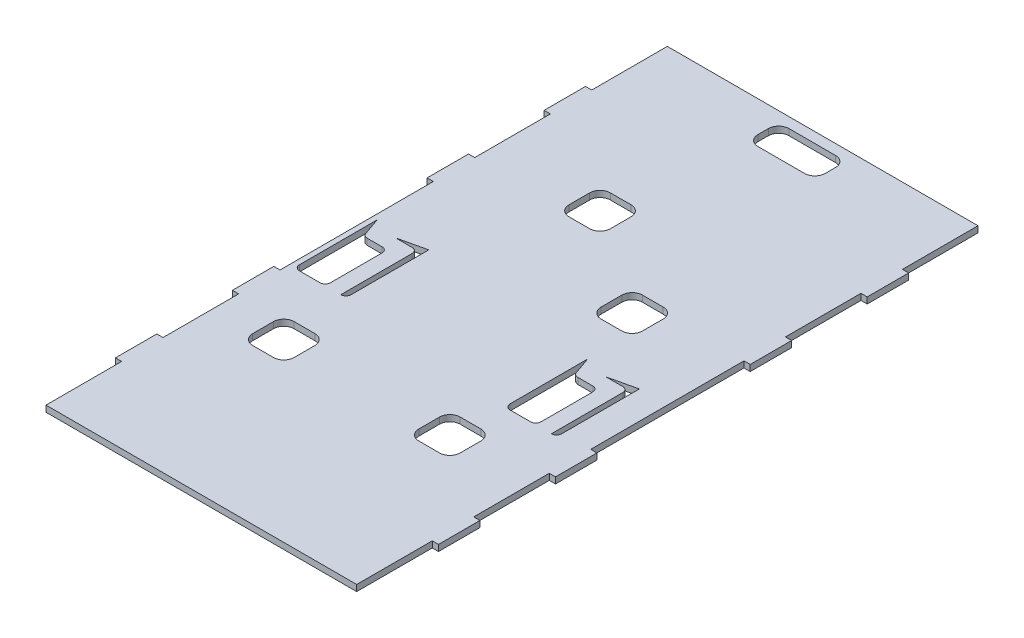
SolidWorks part; units mm, degrees
ref_plane "Front Plane" through (0, 0, 0) normal (0, 0, 1) x (1, 0, 0)
ref_plane "Top Plane" through (0, 0, 0) normal (0, 1, 0) x (1, 0, 0)
ref_plane "Right Plane" through (0, 0, 0) normal (1, 0, 0) x (0, 0, -1)
sketch "Sketch1" plane through (0, 0, 0) normal (0, 1, 0) x (1, 0, 0)
  line L0 (-157.4085, 145.5571) -> (-157.4085, 72.5571)
  line L1 (-157.4085, 258.5571) -> (142.5915, 258.5571)
  line L2 (-157.4085, 258.5571) -> (-157.4085, 185.5571)
  line L3 (-157.4085, -341.4429) -> (142.5915, -341.4429)
  line L4 (142.5915, 258.5571) -> (142.5915, 185.5571)
  line L9 (-157.4085, 185.5571) -> (-163.4085, 185.5571)
  line L11 (-157.4085, 145.5571) -> (-163.4085, 145.5571)
  line L12 (-163.4085, 185.5571) -> (-163.4085, 145.5571)
  line L13 (-157.4085, 72.5571) -> (-163.4085, 72.5571)
  line L15 (-157.4085, 32.5571) -> (-163.4085, 32.5571)
  line L16 (-163.4085, 72.5571) -> (-163.4085, 32.5571)
  line L17 (-157.4085, -115.4429) -> (-163.4085, -115.4429)
  line L19 (-157.4085, -155.4429) -> (-163.4085, -155.4429)
  line L20 (-163.4085, -115.4429) -> (-163.4085, -155.4429)
  line L21 (-157.4085, -228.4429) -> (-163.4085, -228.4429)
  line L23 (-157.4085, -268.4429) -> (-163.4085, -268.4429)
  line L24 (-163.4085, -228.4429) -> (-163.4085, -268.4429)
  line L25 (-157.4085, 32.5571) -> (-157.4085, -115.4429)
  line L26 (-157.4085, -155.4429) -> (-157.4085, -228.4429)
  line L27 (-157.4085, -268.4429) -> (-157.4085, -341.4429)
  line L28 (142.5915, 145.5571) -> (142.5915, 72.5571)
  line L29 (142.5915, 185.5571) -> (148.5915, 185.5571)
  line L31 (142.5915, 145.5571) -> (148.5915, 145.5571)
  line L32 (148.5915, 185.5571) -> (148.5915, 145.5571)
  line L33 (142.5915, 72.5571) -> (148.5915, 72.5571)
  line L35 (142.5915, 32.5571) -> (148.5915, 32.5571)
  line L36 (148.5915, 72.5571) -> (148.5915, 32.5571)
  line L37 (142.5915, -115.4429) -> (148.5915, -115.4429)
  line L39 (142.5915, -155.4429) -> (148.5915, -155.4429)
  line L40 (148.5915, -115.4429) -> (148.5915, -155.4429)
  line L41 (142.5915, -228.4429) -> (148.5915, -228.4429)
  line L43 (142.5915, -268.4429) -> (148.5915, -268.4429)
  line L44 (148.5915, -228.4429) -> (148.5915, -268.4429)
  line L45 (142.5915, 32.5571) -> (142.5915, -115.4429)
  line L46 (142.5915, -155.4429) -> (142.5915, -228.4429)
  line L47 (142.5915, -268.4429) -> (142.5915, -341.4429)
  dimension "D1" = 600
  dimension "D2" = 300
  dimension "D3" = 73
  dimension "D4" = 40
  dimension "D5" = 73
  dimension "D6" = 40
  dimension "D7" = 40
  dimension "D8" = 40
  dimension "D9" = 73
  dimension "D10" = 73
  dimension "D11" = 73
  dimension "D12" = 73
  dimension "D13" = 40
  dimension "D14" = 40
  dimension "D15" = 40
  dimension "D16" = 40
  dimension "D17" = 73
  dimension "D18" = 73
  dimension "D19" = 6
  dimension "D20" = 6
  dimension "D21" = 6
  dimension "D22" = 6
  dimension "D23" = 6
  dimension "D24" = 6
  dimension "D25" = 6
  dimension "D26" = 6
extrude "Boss-Extrude1" add sketch "Sketch1" along normal blind 6
sketch "Sketch2" plane through (0, 6, 0) normal (0, 1, 0) x (1, 0, 0)
  line L0 (-17.4085, -341.4429) -> (-17.4085, -191.4429) construction
  line L2 (-157.4085, -341.4429) -> (142.5915, -341.4429) construction
  line L4 (-17.4085, -191.4429) -> (-157.4085, -191.9429) construction
  line L5 (-157.4085, -155.4429) -> (-157.4085, -228.4429) construction
  line L7 (-17.4085, -191.4429) -> (152.9941, -191.4429) construction
  line L9 (-117.4085, -191.8) -> (-77.4085, -191.8)
  line L10 (-117.4085, -191.8) -> (-117.4085, -151.8)
  line L11 (-117.4085, -151.8) -> (-77.4085, -151.8)
  line L12 (-77.4085, -191.8) -> (-77.4085, -151.8)
  line L13 (42.5915, -191.4429) -> (82.5915, -191.4429)
  line L14 (42.5915, -191.4429) -> (42.5915, -151.4429)
  line L15 (42.5915, -151.4429) -> (82.5915, -151.4429)
  line L16 (82.5915, -191.4429) -> (82.5915, -151.4429)
  dimension "D1" = 140
  dimension "D2" = 150
  dimension "D3" = 40
  dimension "D4" = 40
  dimension "D5" = 40
  dimension "D6" = 40
  dimension "D7" = 120
  dimension "D8" = 60
extrude "Cut-Extrude1" cut sketch "Sketch2" against normal blind 10
fillet "Fillet1" radius 10 8 edges at (42.5915, 3, 191.4429) (42.5915, 3, 151.4429) (82.5915, 3, 151.4429) (82.5915, 3, 191.4429) (-77.4085, 3, 191.8) (-117.4085, 3, 191.8) (-77.4085, 3, 151.8) (-117.4085, 3, 151.8)
sketch "Sketch3" plane through (0, 6, 0) normal (0, 1, 0) x (1, 0, 0)
  line L4 (-102.4085, -26.8) -> (-102.4085, -106.8)
  line L5 (-152.4085, -106.8) -> (-122.4085, -106.8)
  line L7 (-122.4085, -106.8) -> (-122.4085, -46.8)
  line L8 (-122.4085, -46.8) -> (-145.4085, -46.8)
  line L9 (-145.4085, -46.8) -> (-152.4085, -26.8)
  line L10 (-102.4085, -106.8) -> (-107.4085, -106.8)
  line L12 (-107.4085, -32.8) -> (-128.4085, -32.8)
  line L13 (-128.4085, -32.8) -> (-102.4085, -26.8)
  line L15 (-152.4085, -26.8) -> (-152.4085, -106.8)
  line L16 (-157.4085, 32.5571) -> (-157.4085, -115.4429) construction
  line L17 (-107.4085, -32.8) -> (-107.4085, -106.8)
  line L18 (-87.4085, -151.8) -> (-107.4085, -151.8) construction
  dimension "D2" = 80
  dimension "D3" = 50
  dimension "D4" = 80
  dimension "D5" = 30
  dimension "D6" = 5
  dimension "D7" = 23
  dimension "D8" = 21
  dimension "D9" = 14
  dimension "D10" = 60
  dimension "D11" = 45
  dimension "D12" = 5
  dimension "D13" = 45
  dimension "D14" = 7.8102
sketch "Sketch4" plane through (0, 6, 0) normal (0, 1, 0) x (1, 0, 0)
  line L2 (65.5915, -41.4429) -> (65.5915, -121.4429)
  line L6 (72.5915, -61.4429) -> (95.5915, -61.4429)
  line L7 (65.5915, -41.4429) -> (72.5915, -61.4429)
  line L8 (95.5915, -61.4429) -> (95.5915, -121.4429)
  line L9 (65.5915, -121.4429) -> (95.5915, -121.4429)
  line L11 (115.5915, -41.4429) -> (89.5915, -47.4429)
  line L12 (89.5915, -47.4429) -> (110.5915, -47.4429)
  line L13 (110.5915, -47.4429) -> (110.5915, -121.4429)
  line L15 (110.5915, -121.4429) -> (115.5915, -121.4429)
  line L16 (115.5915, -41.4429) -> (115.5915, -121.4429)
  dimension "D1" = 80
  dimension "D2" = 50
  dimension "D3" = 14
  dimension "D4" = 60
  dimension "D5" = 50
  dimension "D6" = 30
  dimension "D8" = 23
  dimension "D9" = 21
  dimension "D10" = 5
extrude "Cut-Extrude4" cut sketch "Sketch3" against normal blind 16
fillet "Fillet2" radius 5 3 edges at (-107.4085, 3, 32.8) (-122.4085, 3, 46.8) (-145.4085, 3, 46.8)
fillet "Fillet3" radius 5 3 edges at (-102.4085, 3, 106.8) (-122.4085, 3, 106.8) (-152.4085, 3, 106.8)
extrude "Cut-Extrude5" cut sketch "Sketch4" against normal blind 16
fillet "Fillet4" radius 5 6 edges at (95.5915, 3, 61.4429) (115.5915, 3, 121.4429) (95.5915, 3, 121.4429) (65.5915, 3, 121.4429) (110.5915, 3, 47.4429) (72.5915, 3, 61.4429)
sketch "Sketch5" plane through (0, 6, 0) normal (0, 1, 0) x (1, 0, 0)
  line L0 (-52.4085, -341.4429) -> (-52.4085, 88.5571) construction
  line L1 (-157.4085, -341.4429) -> (142.5915, -341.4429) construction
  line L3 (48.5915, -341.4429) -> (48.5915, 18.5571) construction
  line L4 (48.5915, 18.5571) -> (142.5915, 18.5571) construction
  line L5 (142.5915, -115.4429) -> (142.5915, 32.5571) construction
  line L6 (-52.4085, 88.5571) -> (-157.4085, 88.5571) construction
  line L7 (-157.4085, 145.5571) -> (-157.4085, 72.5571) construction
  line L9 (-72.4085, 68.5571) -> (-32.4085, 68.5571)
  line L10 (-72.4085, 68.5571) -> (-72.4085, 108.5571)
  line L11 (-72.4085, 108.5571) -> (-32.4085, 108.5571)
  line L12 (-32.4085, 68.5571) -> (-32.4085, 108.5571)
  line L13 (-72.4085, 68.5571) -> (-32.4085, 108.5571) construction
  line L14 (-72.4085, 108.5571) -> (-32.4085, 68.5571) construction
  line L15 (68.5915, -1.4429) -> (28.5915, -1.4429)
  line L16 (68.5915, -1.4429) -> (68.5915, 38.5571)
  line L17 (68.5915, 38.5571) -> (28.5915, 38.5571)
  line L18 (28.5915, -1.4429) -> (28.5915, 38.5571)
  line L19 (68.5915, -1.4429) -> (28.5915, 38.5571) construction
  line L20 (68.5915, 38.5571) -> (28.5915, -1.4429) construction
  dimension "D1" = 430
  dimension "D2" = 105
  dimension "D3" = 94
  dimension "D4" = 360
  dimension "D5" = 40
  dimension "D6" = 40
  dimension "D7" = 40
  dimension "D8" = 40
extrude "Cut-Extrude6" cut sketch "Sketch5" against normal blind 16
fillet "Fillet5" radius 10 8 edges at (68.5915, 3, -38.5571) (68.5915, 3, 1.4429) (28.5915, 3, -38.5571) (28.5915, 3, 1.4429) (-72.4085, 3, -68.5571) (-32.4085, 3, -108.5571) (-32.4085, 3, -68.5571) (-72.4085, 3, -108.5571)
sketch "Sketch6" plane through (0, 6, 0) normal (0, 1, 0) x (1, 0, 0)
  line L0 (-7.4085, 258.5571) -> (-7.4085, -341.4429) construction
  line L1 (142.5915, 258.5571) -> (-157.4085, 258.5571) construction
  line L2 (-157.4085, -341.4429) -> (142.5915, -341.4429) construction
  line L4 (-39.9085, 218.5571) -> (25.0915, 218.5571)
  line L5 (-39.9085, 218.5571) -> (-39.9085, 248.5571)
  line L6 (-39.9085, 248.5571) -> (25.0915, 248.5571)
  line L7 (25.0915, 218.5571) -> (25.0915, 248.5571)
  line L8 (-39.9085, 218.5571) -> (25.0915, 248.5571) construction
  line L9 (-39.9085, 248.5571) -> (25.0915, 218.5571) construction
  point P6 (-7.4085, 233.5571)
  dimension "D1" = 65
  dimension "D2" = 30
  dimension "D3" = 10
extrude "Cut-Extrude7" cut sketch "Sketch6" against normal blind 16
fillet "Fillet6" radius 10 4 edges at (25.0915, 3, -218.5571) (-39.9085, 3, -218.5571) (25.0915, 3, -248.5571) (-39.9085, 3, -248.5571)
